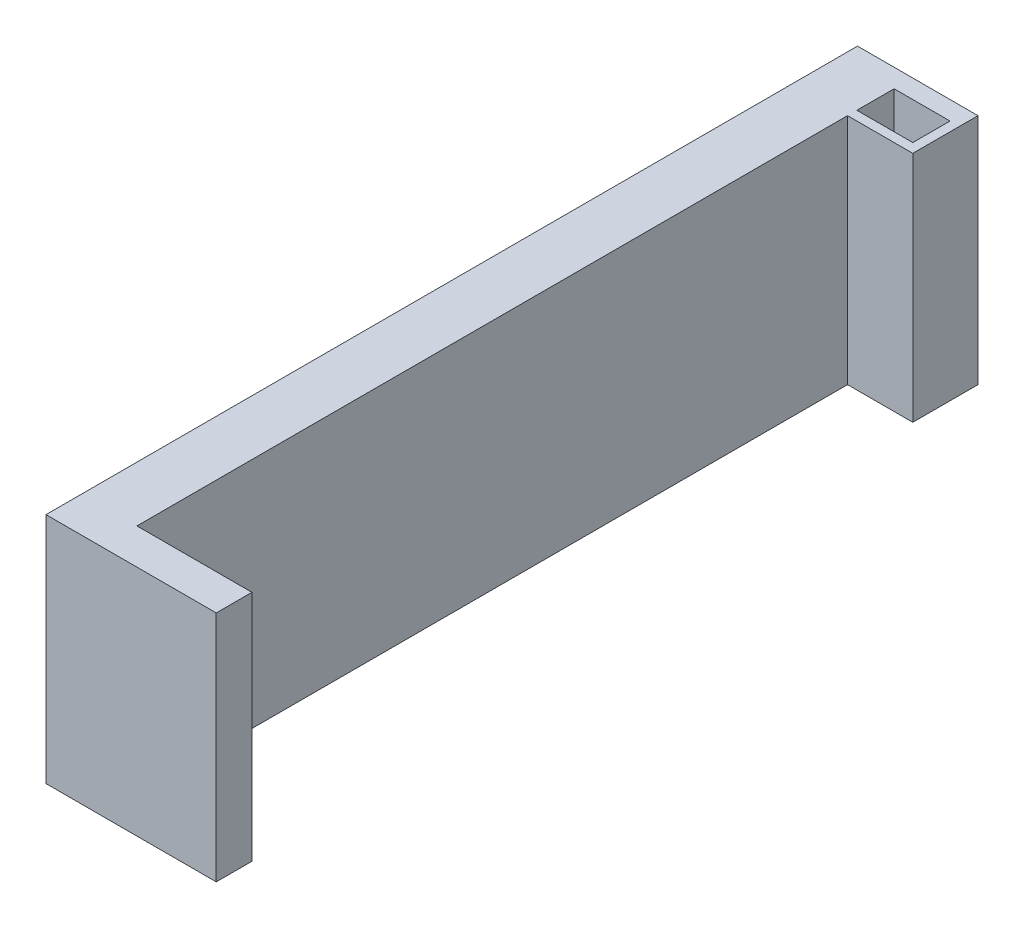
SolidWorks part; units mm, degrees
ref_plane "Piano frontale" through (0, 0, 0) normal (0, 0, 1) x (1, 0, 0)
ref_plane "Piano superiore" through (0, 0, 0) normal (0, 1, 0) x (1, 0, 0)
ref_plane "Piano destro" through (0, 0, 0) normal (1, 0, 0) x (0, 0, -1)
sketch "Schizzo2" plane through (0, 0, 0) normal (0, 0, 1) x (1, 0, 0)
  line L0 (-2.965, 0) -> (2.965, 0)
  line L1 (-2.965, 0) -> (-2.965, 25)
  line L2 (-2.965, 25) -> (2.965, 25)
  line L3 (2.965, 25) -> (2.965, 0)
  point P3 (0, 0)
extrude "Estrusione-Estrusione1" add sketch "Schizzo2" against normal blind 83.26
sketch "Schizzo3" plane through (2.965, 0, 0) normal (1, 0, 0) x (0, 0, -1)
  line L0 (83.26, 25) -> (81.26, 25)
  line L1 (83.26, 25) -> (0, 25) construction
  line L2 (81.26, 25) -> (81.26, 0)
  line L3 (83.26, 0) -> (0, 0) construction
  line L4 (81.26, 0) -> (83.26, 0)
  line L5 (83.26, 0) -> (83.26, 25)
extrude "Estrusione-Estrusione2" add sketch "Schizzo3" along normal blind 7
sketch "Schizzo4" plane through (0, 0, -81.26) normal (0, 0, 1) x (1, 0, 0)
  line L0 (9.965, 25) -> (8.965, 25)
  line L1 (9.965, 25) -> (2.965, 25) construction
  line L2 (8.965, 25) -> (8.965, 0)
  line L3 (9.965, 0) -> (2.965, 0) construction
  line L4 (8.965, 0) -> (9.965, 0)
  line L5 (9.965, 0) -> (9.965, 25)
  dimension "D1" = 1
extrude "Estrusione-Estrusione3" add sketch "Schizzo4" along normal blind 5
sketch "Schizzo5" plane through (8.965, 0, 0) normal (-1, 0, 0) x (0, 0, 1)
  line L0 (-76.26, 25) -> (-77.26, 25)
  line L1 (-76.26, 25) -> (-81.26, 25) construction
  line L2 (-76.26, 0) -> (-77.26, 0)
  line L3 (-76.26, 0) -> (-76.26, 25)
  line L4 (-76.26, 0) -> (-81.26, 0) construction
  line L5 (-77.26, 0) -> (-77.26, 25)
extrude "Estrusione-Estrusione4" add sketch "Schizzo5" along normal up to surface (6 mm away) up to face at (2.965, 12.5, -40.63)
sketch "Schizzo7" plane through (0, 0, 0) normal (0, 0, 1) x (1, 0, 0)
  line L0 (-2.965, 25) -> (-2.965, 0)
  line L1 (-2.965, 0) -> (2.965, 0)
  line L2 (2.965, 0) -> (2.965, 25)
  line L3 (2.965, 25) -> (-2.965, 25)
extrude "Estrusione-Estrusione5" add sketch "Schizzo7" along normal blind 3.83
sketch "Schizzo8" plane through (-2.965, 0, 0) normal (-1, 0, 0) x (0, 0, 1)
  line L0 (3.83, 25) -> (0, 25)
  line L1 (-83.26, 25) -> (3.83, 25) construction
  line L2 (0, 25) -> (0, 0)
  line L3 (0, 0) -> (3.83, 0)
  line L4 (3.83, 0) -> (3.83, 25)
sketch "Schizzo9" plane through (2.965, 0, 0) normal (1, 0, 0) x (0, 0, -1)
  line L0 (-3.83, 25) -> (0, 25)
  line L1 (0, 25) -> (0, 0)
  line L2 (0, 0) -> (-3.83, 0)
  line L3 (-3.83, 0) -> (-3.83, 25)
extrude "Estrusione-Estrusione7" add sketch "Schizzo9" along normal blind 12.34
